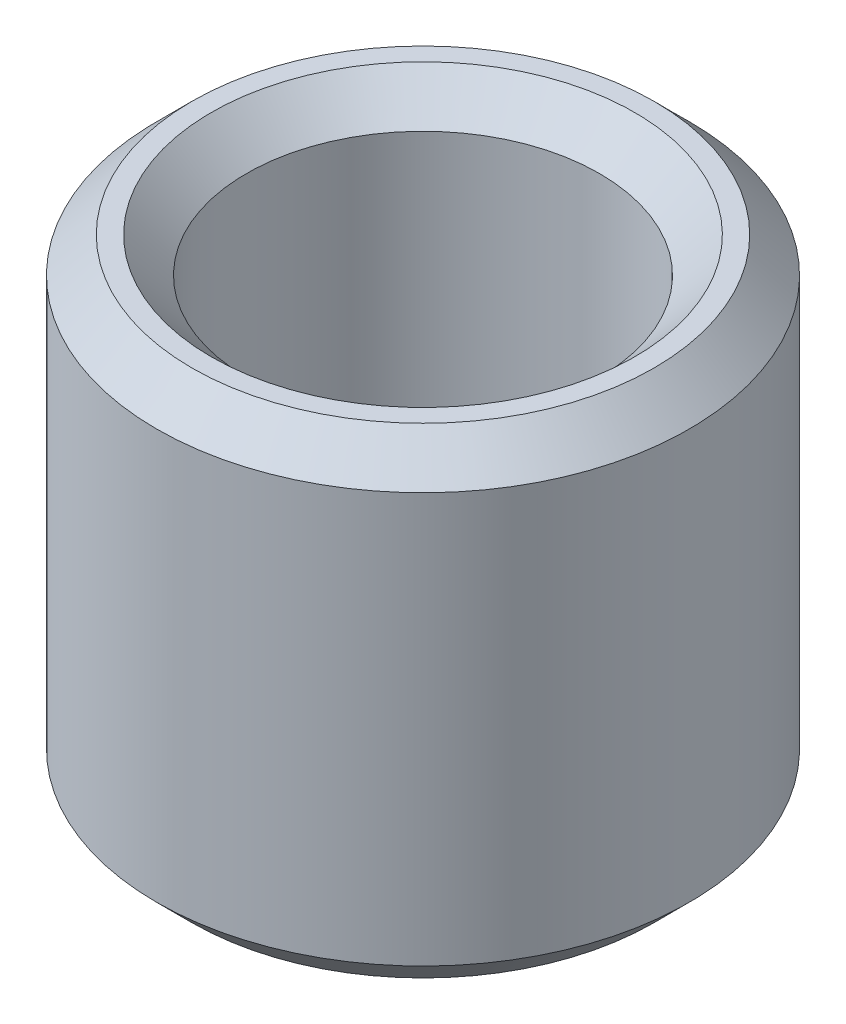
SolidWorks part; units mm, degrees
ref_plane "Front Plane" through (0, 0, 0) normal (0, 0, 1) x (1, 0, 0)
ref_plane "Top Plane" through (0, 0, 0) normal (0, 1, 0) x (1, 0, 0)
ref_plane "Right Plane" through (0, 0, 0) normal (1, 0, 0) x (0, 0, -1)
sketch "Sketch1" plane through (0, 0, 0) normal (0, 1, 0) x (1, 0, 0)
  circle A0 centre (0, 0) radius 15
  dimension "SLEEVE_OD" = 30
extrude "Boss-Extrude1" add sketch "Sketch1" along normal blind 27.0609
sketch "Sketch2" plane through (0, 0, 0) normal (0, 1, 0) x (1, 0, 0)
  circle A0 centre (0, 0) radius 9.9402
  dimension "BORE_D" = 19.8804
extrude "Cut-Extrude1" cut sketch "Sketch2" along normal through all
chamfer "Chamfer1" distance 1.9853 angle 45 4 edges at (0, 27.0609, 9.9402) (0, 0, 9.9402) (0, 0, 15) (0, 27.0609, 15)
